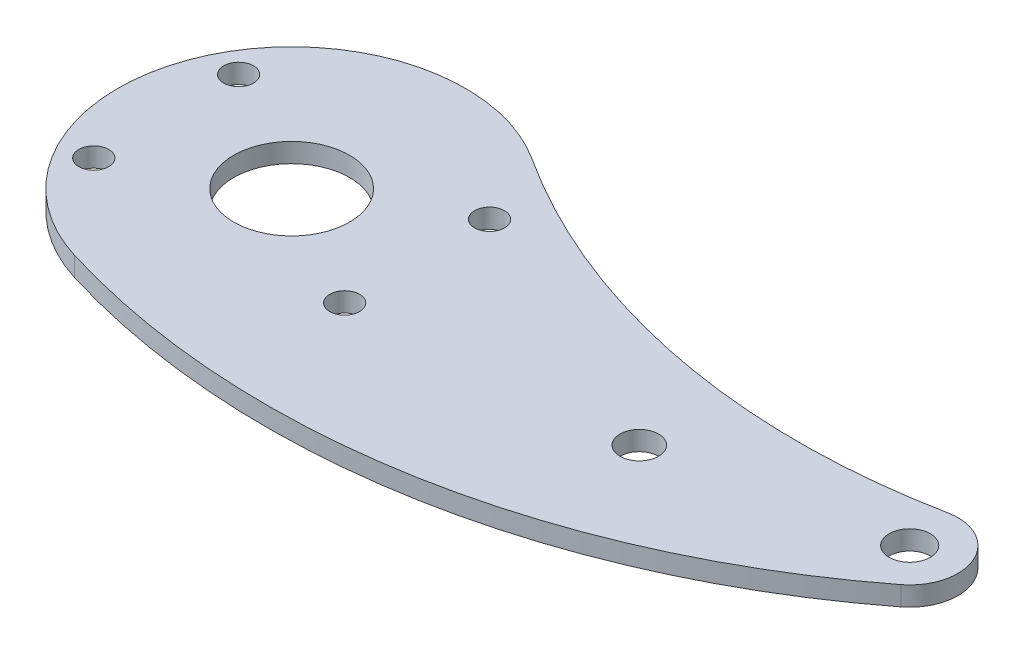
SolidWorks part; units mm, degrees
material "6061-T6 (SS)"
ref_plane "Front" through (0, 0, 0) normal (0, 0, 1) x (1, 0, 0)
ref_plane "Top" through (0, 0, 0) normal (0, 1, 0) x (1, 0, 0)
ref_plane "Right" through (0, 0, 0) normal (1, 0, 0) x (0, 0, -1)
sketch "Sketch1" plane through (0, 0, 0) normal (0, 1, 0) x (1, 0, 0)
  arc A0 (15.5451, 23.9767) -> (-8.3356, -27.3322) centre (0, 0) ccw
  circle A1 centre (0, 0) radius 9.525
  arc A2 (106.4592, -6.2763) -> (100.0497, 7.7846) centre (101.6, 0) ccw
  circle A3 centre (101.6, 0) radius 3.3782
  arc A5 (15.5451, 23.9767) -> (100.0497, 7.7846) centre (77.7255, 119.8833) ccw
  arc A6 (-8.3356, -27.3322) -> (106.4592, -6.2763) centre (28.7114, 94.1442) ccw
  dimension "D2" = 57.15
  dimension "D3" = 15.875
  dimension "D4" = 6.7564
  dimension "D1" = 19.05
  dimension "D6" = 114.3
  dimension "D7" = 127
  dimension "D5" = 101.6
extrude "Boss-Extrude1" add sketch "Sketch1" along normal blind 3.175 contours A2 A0 | A0 | A2 A3 region at (31.3101, 0, 5.5999)
sketch "Sketch4" plane through (0, 3.175, 0) normal (0, 1, 0) x (1, 0, 0)
  circle A0 centre (0, 0) radius 23.8125
  point P7 (-20.6222, 11.9062)
  point P9 (20.6222, 11.9062)
  point P11 (20.6222, -11.9062)
  point P13 (-20.6222, -11.9062)
  dimension "D1" = 47.625
  dimension "D2" = 23.8125
hole_wizard "#10 (0.1935) Diameter Hole1" positions "Sketch4" profile "Sketch3" hole size "#10" standard "ANSI Inch" end condition through all
sketch "Sketch3" plane through (-20.6222, 3.175, 11.9062) normal (1, 0, 0) x (0, 0, 1)
  line L0 (0, 0) -> (0, 3.175)
  line L1 (0, 3.175) -> (2.4574, 3.175)
  line L2 (2.4574, 3.175) -> (2.4574, 0)
  line L5 (2.4574, 0) -> (0, 0)
  line L11 (0, -6.35) -> (0, 107.95) construction
  dimension "Thru Hole Dia." = 4.9149
  dimension "Thru Hole Depth" = 3.175
sketch "Sketch7" plane through (0, 3.175, 0) normal (0, 1, 0) x (1, 0, 0)
  line L3 (65.0875, -7.9375) -> (101.6, 0) construction
  line L6 (0, 0) -> (101.6, 0) construction
  circle A0 centre (101.6, 0) radius 3.3782 construction
  point P0 (65.0875, -7.9375)
  dimension "D1" = 7.9375
  dimension "D2" = 36.5125
hole_wizard "1/4 (0.25) Diameter Hole2" positions "Sketch7" profile "Sketch8" hole size "1/4" standard "ANSI Inch" end condition through all
sketch "Sketch8" plane through (65.0875, 3.175, 7.9375) normal (1, 0, 0) x (0, 0, 1)
  line L0 (0, 0) -> (0, 3.175)
  line L1 (0, 3.175) -> (3.175, 3.175)
  line L2 (3.175, 3.175) -> (3.175, 0)
  line L5 (3.175, 0) -> (0, 0)
  line L11 (0, -6.35) -> (0, 107.95) construction
  dimension "Thru Hole Dia." = 6.35
  dimension "Thru Hole Depth" = 3.175
